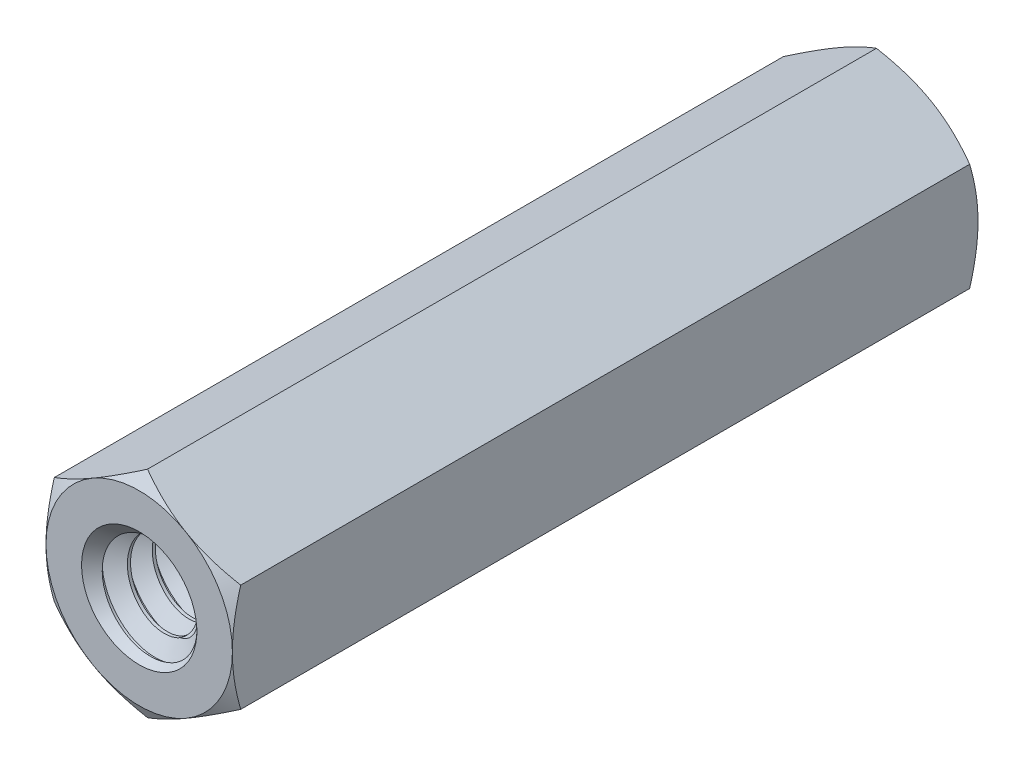
SolidWorks part; units mm, degrees
ref_plane "Front Plane" through (0, 0, 0) normal (0, 0, 1) x (1, 0, 0)
ref_plane "Top Plane" through (0, 0, 0) normal (0, 1, 0) x (1, 0, 0)
ref_plane "Right Plane" through (0, 0, 0) normal (1, 0, 0) x (0, 0, -1)
sketch "Sketch3" plane through (0, 0, 0) normal (1, 0, 0) x (0, 0, -1)
  line L0 (-9.525, 0) -> (9.525, 0) construction
  line L1 (0, 2.3813) -> (0, -2.3813) construction
  line L2 (-9.525, 1.4224) -> (-9.525, -1.4224) construction
  point P2 (-6.35, 0)
  point P3 (6.35, 0)
  dimension "D1" = 15.875
  dimension "Length" = 19.05
  dimension "Min Thread Length" = 15.875
  dimension "Thread Dia" = 2.8448
  dimension "Hex" = 4.7625
sketch "Sketch1" plane through (0, 0, 0) normal (0, 0, 1) x (1, 0, 0)
  line L1 (0, 2.7496) -> (-2.3813, 1.3748)
  line L2 (-2.3813, 1.3748) -> (-2.3813, -1.3748)
  line L3 (-2.3813, -1.3748) -> (0, -2.7496)
  line L4 (0, -2.7496) -> (2.3813, -1.3748)
  line L5 (2.3813, -1.3748) -> (2.3812, 1.3748)
  line L6 (2.3812, 1.3748) -> (0, 2.7496)
  circle A0 centre (0, 0) radius 2.3813 construction
  circle A1 centre (0, 0) radius 1.4224
extrude "Extrude1" add sketch "Sketch1" along normal up to vertex (9.525 mm away) and the other way up to vertex (9.525 mm away) up to point (0, 0, 9.525) other way up to point (0, 0, -9.525)
sketch "Sketch11" plane through (0, 0, -9.525) normal (0, 0, -1) x (-1, 0, 0)
  circle A0 centre (0, 0) radius 1.4224 construction
  circle A1 centre (0, 0) radius 1.4224
curve "Helix/Spiral1" pitch 0.635 height 19.685 radius 1.4224 centre (0, 0, -9.525) axis (0, 0, 1) start towards (0, 1, 0) parameters "Pitch"=0.635
sketch "Sketch12" plane through (0, 0, 0) normal (1, 0, 0) x (0, 0, -1)
  line L0 (10.0806, 1.4224) -> (9.525, 1.4224)
  line L1 (10.0806, 1.4224) -> (9.8425, 1.01)
  line L2 (9.8425, 1.01) -> (9.7631, 1.01)
  line L3 (9.7631, 1.01) -> (9.525, 1.4224)
  line L4 (9.8028, 1.01) -> (9.8028, 1.4224) construction
  line L5 (9.9616, 1.2162) -> (9.6441, 1.2162) construction
  dimension "D1" = 0.0794
  dimension "D2" = 0.3175
  dimension "D3" = 60
sweep "Sweep1" add profiles "Sketch12" path "Helix/Spiral1"
sketch "Sketch6" plane through (0, 0, -9.525) normal (0, 0, -1) x (-1, 0, 0)
  line L6 (0, 2.7496) -> (-2.3812, 1.3748)
  line L7 (-2.3812, 1.3748) -> (-2.3813, -1.3748)
  line L8 (-2.3813, -1.3748) -> (0, -2.7496)
  line L9 (0, -2.7496) -> (2.3813, -1.3748)
  line L10 (2.3813, -1.3748) -> (2.3813, 1.3748)
  line L11 (2.3813, 1.3748) -> (0, 2.7496)
  line L12 (0, 2.7496) -> (-2.3812, 1.3748)
  line L13 (-2.3812, 1.3748) -> (-2.3813, -1.3748)
  line L14 (-2.3813, -1.3748) -> (0, -2.7496)
  line L15 (0, -2.7496) -> (2.3813, -1.3748)
  line L16 (2.3813, -1.3748) -> (2.3813, 1.3748)
  line L17 (2.3813, 1.3748) -> (0, 2.7496)
  dimension "D1" = 0
extrude "Extrude2" cut sketch "Sketch6" along normal through all
sketch "Sketch7" plane through (0, 0, -9.525) normal (0, 0, -1) x (-1, 0, 0)
  circle A2 centre (0, 0) radius 1.4732
  circle A3 centre (0, 0) radius 1.4732
  dimension "D1" = 0.0508
extrude "Extrude3" cut sketch "Sketch7" against normal through all draft 43
sketch "Sketch8" plane through (0, 0, -9.525) normal (0, 0, -1) x (-1, 0, 0)
  circle A0 centre (0, 0) radius 2.3813 construction
  circle A1 centre (0, 0) radius 2.3813
extrude "Extrude4" cut sketch "Sketch8" against normal through all draft 60 flip side to cut
mirror "Mirror1" about plane through (0, 0, 0) normal (0, 0, 1) of "Extrude2", "Extrude3", "Extrude4"
sketch "Sketch9" [suppressed] plane through (0, 0, 0) normal (1, 0, 0) x (0, 0, -1)
  line L1 (-22.225, 3.2258) -> (22.225, 3.2258)
  line L2 (-22.225, 3.2258) -> (-22.225, 0)
  line L3 (-22.225, 0) -> (22.225, 0)
  line L4 (22.225, 3.2258) -> (22.225, 0)
  line L7 (-38.1, 0) -> (38.1, 0) construction
revolve "Revolve" [suppressed] add sketch "Sketch9" angle 360 about L0
sketch "Sketch10" [suppressed] plane through (0, 0, 0) normal (1, 0, 0) x (0, 0, -1)
  line L0 (38.1, 3.175) -> (22.225, 3.175)
  line L1 (-38.1, 3.175) -> (-22.225, 3.175)
  line L2 (22.225, 3.175) -> (22.225, -3.175)
  line L3 (-38.1, -3.2258) -> (-22.225, -3.2258)
  line L4 (-22.225, 3.175) -> (-22.225, -3.2258)
  line L5 (22.225, -3.175) -> (38.1, -3.175)
equation "\"D1@Sketch3\" = \"Min Thread Length@Sketch3\""
equation "\"D3@Helix/Spiral1\" = \"Length@Sketch3\"+\"Pitch@Helix/Spiral1\""
equation "\"D1@Sketch12\" = \"Pitch@Helix/Spiral1\"*.125"
equation "\"D2@Sketch12\" = \"Pitch@Helix/Spiral1\"*.5"
